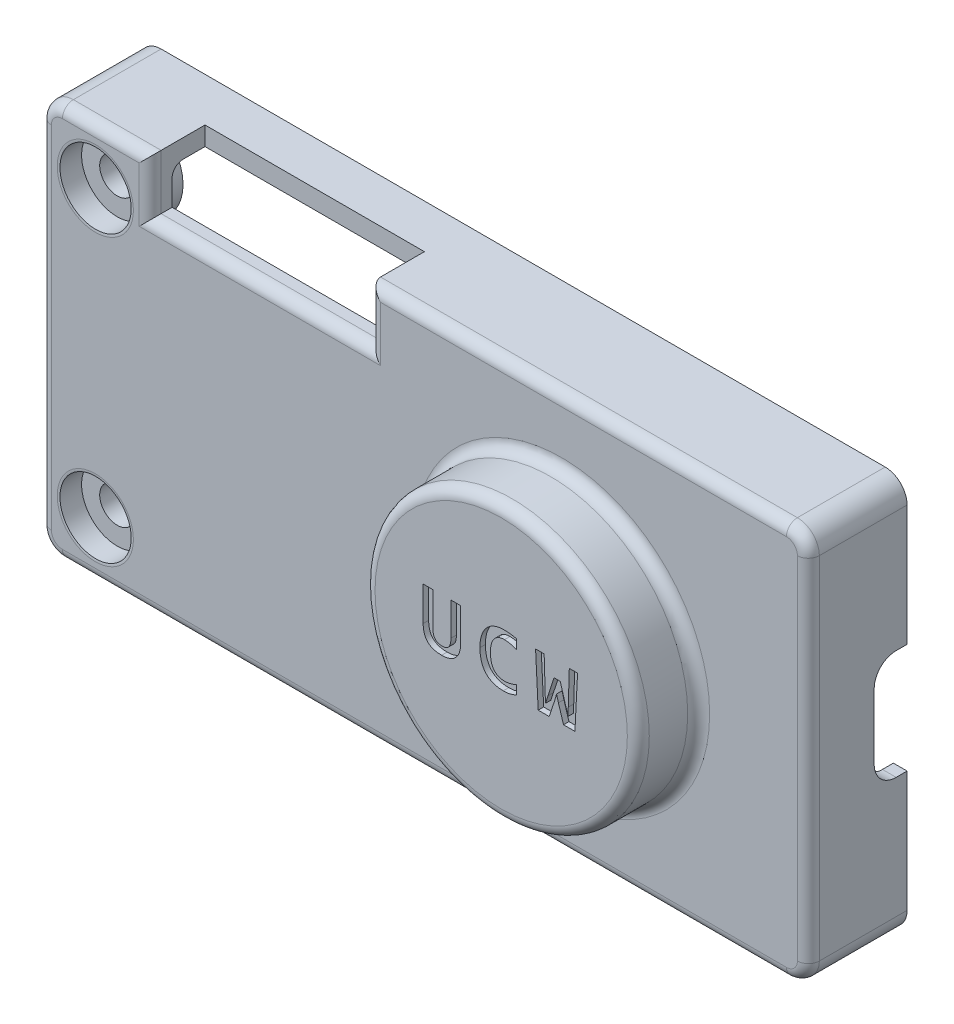
SolidWorks part; units mm, degrees
ref_plane "Alzado" through (0, 0, 0) normal (0, 0, 1) x (1, 0, 0)
ref_plane "Planta" through (0, 0, 0) normal (0, 1, 0) x (1, 0, 0)
ref_plane "Vista lateral" through (0, 0, 0) normal (1, 0, 0) x (0, 0, -1)
sketch "Croquis1" plane through (0, 0, 0) normal (0, 0, 1) x (1, 0, 0)
  line L5 (-19.6625, 44.07) -> (50.3375, 44.07)
  line L7 (-19.6625, 44.07) -> (-19.6625, 8.07)
  line L8 (-19.6625, 8.07) -> (50.3375, 8.07)
  line L9 (50.3375, 44.07) -> (50.3375, 8.07)
  point P0 (0, 0)
extrude "Saliente-Extruir1" add sketch "Croquis1" along normal blind 2
sketch "Croquis2" plane through (0, 0, 2) normal (0, 0, 1) x (1, 0, 0)
  line L0 (50.3375, 26.07) -> (27.8375, 26.07)
  line L1 (50.3375, 8.07) -> (50.3375, 44.07) construction
  line L2 (27.8375, 26.07) -> (27.8375, 25.57)
  circle A0 centre (27.8375, 25.57) radius 12.5
extrude "Saliente-Extruir2" add sketch "Croquis2" along normal blind 5.5 contours A0 region at (15.6935, 25.3271, 2)
sketch "Croquis3" plane through (0, 0, 0) normal (0, 0, -1) x (-1, 0, 0)
  line L0 (-48.5875, 42.3632) -> (17.9125, 42.3632)
  line L1 (-50.3375, 44.07) -> (19.6625, 44.07)
  line L2 (-50.3375, 44.07) -> (-50.3375, 8.07)
  line L3 (-50.3375, 8.07) -> (19.6625, 8.07)
  line L4 (19.6625, 44.07) -> (19.6625, 8.07)
  line L13 (17.9125, 9.8632) -> (-48.5875, 9.8632)
  line L14 (17.9125, 9.8632) -> (17.9125, 42.3632)
  line L16 (-48.5875, 9.8632) -> (-48.5875, 42.3632)
  line M10 (19.6625, 8.07) -> (19.6625, 44.07)
  line M11 (19.6625, 44.07) -> (-50.3375, 44.07)
  line M12 (-50.3375, 44.07) -> (-50.3375, 8.07)
  line M13 (-50.3375, 8.07) -> (19.6625, 8.07)
extrude "Saliente-Extruir3" add sketch "Croquis3" along normal blind 5 contours L13 L16 L0 L14 M13 M10 M11 M12 region at (15.3375, 43.2829, 0)
sketch "Croquis4" plane through (0, 0, 0) normal (0, 0, -1) x (-1, 0, 0)
  circle A0 centre (-27.8375, 25.57) radius 11
extrude "Cortar-Extruir1" cut sketch "Croquis4" against normal blind 6
sketch "Croquis5" plane through (0, 0, 0) normal (0, 0, -1) x (-1, 0, 0)
  line L0 (-48.5875, 9.7768) -> (-42.5875, 9.7768)
  line L1 (-48.5875, 42.3632) -> (-45.5875, 42.3632)
  line L2 (-45.5875, 42.3632) -> (-45.5875, 39.3632)
  line L4 (-48.5875, 42.3632) -> (-48.5875, 36.3632)
  line L8 (-48.5875, 42.3632) -> (-42.5875, 42.3632)
  line L9 (-48.5875, 9.7768) -> (-48.5875, 15.7768)
  line L12 (-15.3375, 42.3632) -> (-15.3375, 56.0017)
  line L13 (17.9125, 42.3632) -> (-48.5875, 42.3632) construction
  line L18 (-50.3375, 26.07) -> (-56.6111, 26.07)
  line L19 (-50.3375, 44.07) -> (-50.3375, 8.07) construction
  line L20 (-45.5875, 9.7768) -> (-45.5875, 12.7768)
  line L21 (-48.5875, 9.7768) -> (-45.5875, 9.7768)
  line L22 (17.9125, 9.7768) -> (14.9125, 9.7768)
  line L23 (14.9125, 9.7768) -> (14.9125, 12.7768)
  line L24 (17.9125, 9.7768) -> (17.9125, 15.7768)
  line L25 (17.9125, 42.3632) -> (11.9125, 42.3632)
  line L26 (17.9125, 42.3632) -> (17.9125, 36.3632)
  line L27 (14.9125, 42.3632) -> (14.9125, 39.3632)
  line L28 (17.9125, 42.3632) -> (14.9125, 42.3632)
  line L29 (17.9125, 9.7768) -> (11.9125, 9.7768)
  arc A3 (-48.5875, 36.3632) -> (-42.5875, 42.3632) centre (-45.5875, 39.3632) ccw
  arc A8 (-48.5875, 15.7768) -> (-42.5875, 9.7768) centre (-45.5875, 12.7768) cw
  arc A9 (17.9125, 15.7768) -> (11.9125, 9.7768) centre (14.9125, 12.7768) ccw
  arc A10 (17.9125, 36.3632) -> (11.9125, 42.3632) centre (14.9125, 39.3632) cw
extrude "Saliente-Extruir4" add sketch "Croquis5" along normal blind 2 contours A3 | A8 | A10 L25 | A9 region at (45.1985, 38.9743, 0) region at (-14.5235, 38.9743, 0) region at (-14.5193, 13.204, 0) region at (45.1943, 13.204, 0)
sketch "Croquis14" plane through (0, 0, -5) normal (0, 0, -1) x (-1, 0, 0)
  line L1 (-50.3375, 44.07) -> (19.6625, 44.07)
  line L2 (-50.3375, 44.07) -> (-50.3375, 8.07)
  line L3 (-50.3375, 8.07) -> (19.6625, 8.07)
  line L4 (19.6625, 44.07) -> (19.6625, 8.07)
  line L5 (17.9125, 9.8632) -> (-48.5875, 9.8632)
  line L6 (17.9125, 9.8632) -> (17.9125, 42.3632)
  line L7 (17.9125, 42.3632) -> (-48.5875, 42.3632)
  line L8 (-48.5875, 9.8632) -> (-48.5875, 42.3632)
extrude "Saliente-Extruir5" add sketch "Croquis14" along normal blind 2
sketch "Croquis15" plane through (0, 8.07, 0) normal (0, -1, 0) x (1, 0, 0)
  line L0 (50.3375, -7) -> (40.8375, -7)
  line L1 (9.8375, -6) -> (9.8375, -7)
  line L2 (9.8375, -7) -> (40.8375, -7)
  line L3 (40.8375, -7) -> (40.8375, -3)
  line L4 (40.8375, -3) -> (9.8375, -3)
  line L5 (9.8375, -3) -> (9.8375, -6)
  line L6 (50.3375, -7) -> (-19.6625, -7) construction
  line M9 (-19.6625, -7) -> (50.3375, -7)
extrude "Cortar-Extruir7" cut sketch "Croquis15" against normal blind 2 contours L4 L5 L1 L3 M9 region at (25.3375, 8.07, -5)
sketch "Croquis11" plane through (50.3375, 0, 0) normal (1, 0, 0) x (0, 0, -1)
  line L1 (7, 31.07) -> (4, 31.07)
  line L7 (7, 44.07) -> (7, 8.07) construction
  line L8 (7, 31.07) -> (7, 21.07)
  line L10 (4, 31.07) -> (4, 21.07)
  line L11 (4, 21.07) -> (7, 21.07)
extrude "Cortar-Extruir4" cut sketch "Croquis11" against normal blind 10 contours L11 L8 L1 L10
sketch "Croquis16" plane through (0, 44.07, 0) normal (0, 1, 0) x (1, 0, 0)
  line L0 (-19.6625, -2) -> (-9.6625, -2)
  line L1 (50.3375, -2) -> (-19.6625, -2) construction
  line L2 (-9.6625, -2) -> (10.3375, -2)
  line L3 (-9.6625, -2) -> (-9.6625, 3)
  line L4 (-9.6625, 3) -> (10.3375, 3)
  line L5 (10.3375, 3) -> (10.3375, -2)
  line M8 (-19.6625, -2) -> (50.3375, -2)
extrude "Cortar-Extruir8" cut sketch "Croquis16" against normal blind 5 contours L5 L4 L3 M8 region at (0.3375, 44.07, -0.5)
sketch "Croquis17" plane through (0, 0, -7) normal (0, 0, -1) x (-1, 0, 0)
  line L0 (-48.5875, 42.3632) -> (-48.5875, 42.8632)
  line L1 (-48.5875, 42.8632) -> (-49.0875, 42.8632)
  line L2 (17.9125, 9.8632) -> (18.4125, 9.8632)
  line L3 (18.4125, 9.8632) -> (18.4125, 9.3632)
  line L5 (-49.0875, 42.8632) -> (18.4125, 42.8632)
  line L6 (-49.0875, 42.8632) -> (-49.0875, 9.3632)
  line L7 (-49.0875, 9.3632) -> (18.4125, 9.3632)
  line L8 (18.4125, 42.8632) -> (18.4125, 9.3632)
  line L9 (-48.5875, 42.3632) -> (17.9125, 42.3632)
  line L10 (-48.5875, 42.3632) -> (-48.5875, 9.8632)
  line L11 (-48.5875, 9.8632) -> (17.9125, 9.8632)
  line L12 (17.9125, 42.3632) -> (17.9125, 9.8632)
  line M5 (-50.3375, 31.07) -> (-48.5875, 31.07)
  line M6 (-48.5875, 31.07) -> (-48.5875, 42.3632)
  line M7 (-48.5875, 42.3632) -> (17.9125, 42.3632)
  line M8 (17.9125, 42.3632) -> (17.9125, 9.8632)
  line M9 (17.9125, 9.8632) -> (-9.8375, 9.8632)
  line M10 (-9.8375, 9.8632) -> (-9.8375, 8.07)
extrude "Cortar-Extruir9" cut sketch "Croquis17" against normal blind 1.5 contours L1 L6 L0 M5 M6 | L11 L10 L6 L7 M5 M10 | L7 L3 L2 M10 M9 | L8 L5 L0 L2 M7 M8 region at (48.8375, 36.9666, -7) region at (47.8406, 42.6132, -7) region at (49.036, 20.4666, -7) region at (-4.2875, 9.6132, -7)
sketch "Croquis7" plane through (0, 0, 2) normal (0, 0, 1) x (1, 0, 0)
  line L1 (-14.6625, 44.07) -> (-14.6625, 39.07)
  line L2 (-19.6625, 26.07) -> (-23.7953, 26.07)
  line L3 (-19.6625, 44.07) -> (-19.6625, 8.07) construction
  circle A0 centre (-14.6625, 39.07) radius 1.5
  circle A1 centre (-14.6625, 13.07) radius 1.5
hole_wizard "Refrentado para tornillo con cabeza plana de M31" positions "Croquis3D1" profile "Croquis8" counterbore size "M3" standard "DIN" end condition through all
sketch3d "Croquis3D1"
  point P0 (-14.6625, 39.07, 2)
  point P3 (-14.6625, 13.07, 2)
sketch "Croquis8" plane through (-14.6625, 39.07, 2) normal (1, 0, 0) x (0, -1, 0)
  line L0 (0, 0) -> (0, 9)
  line L1 (0, 9) -> (1.6, 9)
  line L3 (1.6, 9) -> (1.6, 2)
  line L4 (3.25, 2) -> (1.6, 2)
  line L5 (3.25, 2) -> (3.25, 0.025)
  line L6 (3.25, 0.025) -> (3.275, 0)
  line L7 (3.275, 0) -> (0, 0)
  line L8 (-3.25, 0.025) -> (-3.275, 0) construction
  line L11 (0, -6.35) -> (0, 107.95) construction
  dimension "Diámetro de taladro hasta el siguiente" = 3.2
  dimension "Profundidad de taladro hasta el siguiente" = 9
  dimension "Diámetro de refrentado" = 6.5
  dimension "Profundidad de refrentado" = 2
  dimension "Diámetro de avellanado cercano" = 6.55
  dimension "Ángulo de avellanado cercano" = 90
fillet "Redondeo1" radius 1 11 edges at (16.8375, 25.57, 0) (16.8375, 25.57, 6) (48.5875, 26.07, 0) (15.3375, 9.8632, 0) (-17.9125, 26.07, 0) (42.6304, 15.8191, 0) (-11.9554, 15.8191, 0) (-11.9125, 36.3632, 0) (42.5875, 36.3632, 0) (-10.7875, 42.3632, 0) (26.4625, 42.3632, 0)
fillet "Redondeo2" radius 1 12 edges at (30.3375, 44.07, 2) (-14.6625, 44.07, 2) (50.3375, 26.07, 2) (15.3375, 8.07, 2) (-19.6625, 26.07, 2) (40.3375, 25.57, 2) (40.3375, 25.57, 7.5) (-11.3875, 13.07, 2) (-11.3875, 39.07, 2) (-9.6625, 41.57, 2) (0.3375, 39.07, 2) (10.3375, 41.57, 2)
fillet "Redondeo3" radius 2 18 edges at (50.0446, 8.3629, 1.7071) (-19.3696, 8.3629, 1.7071) (50.0446, 43.7771, 1.7071) (50.3375, 44.07, -3) (-19.6625, 44.07, -3) (-19.6625, 8.07, -3) (50.3375, 8.07, -3) (48.5875, 9.8632, -3.75) (-17.9125, 9.8632, -3.75) (49.4625, 21.07, -4) (49.4625, 31.07, -4) (-19.3696, 43.7771, 1.7071) (-17.9125, 42.3632, -3.75) (48.5875, 42.3632, -3.75) (49.0875, 9.3632, -6.25) (-18.4125, 9.3632, -6.25) (-18.4125, 42.8632, -6.25) (49.0875, 42.8632, -6.25)
sketch "Croquis13" plane through (0, 0, 7.5) normal (0, 0, 1) x (1, 0, 0)
  text T0 "<b>UCW</b>" font "Consolas" height in points 18
extrude "Cortar-Extruir6" cut sketch "Croquis13" against normal blind 0.5
